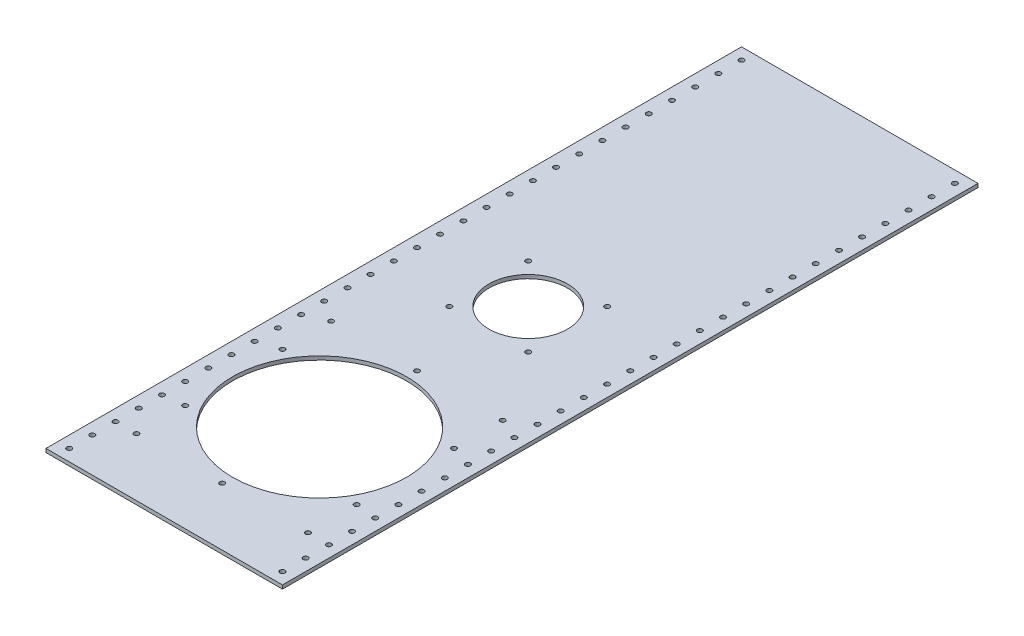
SolidWorks part; units mm, degrees
ref_plane "Front Plane" through (0, 0, 0) normal (0, 0, 1) x (1, 0, 0)
ref_plane "Top Plane" through (0, 0, 0) normal (0, 1, 0) x (1, 0, 0)
ref_plane "Right Plane" through (0, 0, 0) normal (1, 0, 0) x (0, 0, -1)
sketch "Sketch1" plane through (0, 0, 0) normal (0, 1, 0) x (1, 0, 0)
  line L0 (0, 392.549) -> (0, -207.451) construction
  line L1 (-102, -207.451) -> (102, -207.451)
  line L2 (-102, -207.451) -> (-102, 392.549)
  line L3 (-102, 392.549) -> (102, 392.549)
  line L4 (102, -207.451) -> (102, 392.549)
  line L5 (-102, -207.451) -> (102, 392.549) construction
  line L6 (-102, 392.549) -> (102, -207.451) construction
  line L7 (-102, -73.451) -> (102, -73.451) construction
  line L8 (92, 392.549) -> (92, -207.451) construction
  line L9 (-92, 392.549) -> (-92, -207.451) construction
  line L10 (-40, 106.549) -> (40, 106.549) construction
  line L11 (-80, -163.451) -> (80, -163.451) construction
  line L12 (-80, -163.451) -> (-80, 16.549) construction
  line L13 (-80, 16.549) -> (80, 16.549) construction
  line L14 (80, -163.451) -> (80, 16.549) construction
  line L15 (-80, -163.451) -> (80, 16.549) construction
  line L16 (-80, 16.549) -> (80, -163.451) construction
  line L17 (-40, 66.549) -> (40, 66.549) construction
  line L18 (-40, 66.549) -> (-40, 146.549) construction
  line L19 (-40, 146.549) -> (40, 146.549) construction
  line L20 (40, 66.549) -> (40, 146.549) construction
  line L21 (-40, 66.549) -> (40, 146.549) construction
  line L22 (-40, 146.549) -> (40, 66.549) construction
  circle A232 centre (92, 382.549) radius 2.15
  circle A233 centre (92, 362.549) radius 2.15
  circle A234 centre (92, 342.549) radius 2.15
  circle A235 centre (92, 322.549) radius 2.15
  circle A236 centre (92, 302.549) radius 2.15
  circle A237 centre (92, 282.549) radius 2.15
  circle A238 centre (92, 262.549) radius 2.15
  circle A239 centre (92, 242.549) radius 2.15
  circle A240 centre (92, 222.549) radius 2.15
  circle A241 centre (92, 202.549) radius 2.15
  circle A242 centre (92, 182.549) radius 2.15
  circle A243 centre (92, 162.549) radius 2.15
  circle A244 centre (92, 142.549) radius 2.15
  circle A245 centre (92, 122.549) radius 2.15
  circle A246 centre (92, 102.549) radius 2.15
  circle A247 centre (92, 82.549) radius 2.15
  circle A248 centre (92, 62.549) radius 2.15
  circle A249 centre (92, 42.549) radius 2.15
  circle A250 centre (92, 22.549) radius 2.15
  circle A251 centre (92, 2.549) radius 2.15
  circle A252 centre (92, -17.451) radius 2.15
  circle A253 centre (92, -37.451) radius 2.15
  circle A254 centre (92, -57.451) radius 2.15
  circle A255 centre (92, -77.451) radius 2.15
  circle A256 centre (92, -97.451) radius 2.15
  circle A257 centre (92, -117.451) radius 2.15
  circle A258 centre (92, -137.451) radius 2.15
  circle A259 centre (92, -157.451) radius 2.15
  circle A260 centre (92, -177.451) radius 2.15
  circle A261 centre (92, -197.451) radius 2.15
  circle A262 centre (-92, -197.451) radius 2.15
  circle A263 centre (-92, -177.451) radius 2.15
  circle A264 centre (-92, -157.451) radius 2.15
  circle A265 centre (-92, -137.451) radius 2.15
  circle A266 centre (-92, -117.451) radius 2.15
  circle A267 centre (-92, -97.451) radius 2.15
  circle A268 centre (-92, -77.451) radius 2.15
  circle A269 centre (-92, -57.451) radius 2.15
  circle A270 centre (-92, -37.451) radius 2.15
  circle A271 centre (-92, -17.451) radius 2.15
  circle A272 centre (-92, 2.549) radius 2.15
  circle A273 centre (-92, 22.549) radius 2.15
  circle A274 centre (-92, 42.549) radius 2.15
  circle A275 centre (-92, 62.549) radius 2.15
  circle A276 centre (-92, 82.549) radius 2.15
  circle A277 centre (-92, 102.549) radius 2.15
  circle A278 centre (-92, 122.549) radius 2.15
  circle A279 centre (-92, 142.549) radius 2.15
  circle A280 centre (-92, 162.549) radius 2.15
  circle A281 centre (-92, 182.549) radius 2.15
  circle A282 centre (-92, 202.549) radius 2.15
  circle A283 centre (-92, 222.549) radius 2.15
  circle A284 centre (-92, 242.549) radius 2.15
  circle A285 centre (-92, 262.549) radius 2.15
  circle A286 centre (-92, 282.549) radius 2.15
  circle A287 centre (-92, 302.549) radius 2.15
  circle A288 centre (-92, 322.549) radius 2.15
  circle A289 centre (-92, 342.549) radius 2.15
  circle A290 centre (-92, 362.549) radius 2.15
  circle A291 centre (-92, 382.549) radius 2.15
  circle A292 centre (0, -73.451) radius 62.5 construction
  circle A293 centre (-74, -157.451) radius 2.125
  circle A294 centre (-74, -115.451) radius 2.125
  circle A296 centre (0, -157.451) radius 2.125
  circle A297 centre (74, -157.451) radius 2.125
  circle A298 centre (74, -115.451) radius 2.125
  circle A299 centre (74, -31.451) radius 2.125
  circle A300 centre (74, 10.549) radius 2.125
  circle A301 centre (0, 10.549) radius 2.125
  circle A302 centre (-74, 10.549) radius 2.125
  circle A303 centre (-74, -31.451) radius 2.125
  circle A304 centre (0, 106.549) radius 33.85
  circle A310 centre (0, -73.451) radius 75.125
  circle A313 centre (-34, 72.549) radius 2.15
  circle A314 centre (34, 72.549) radius 2.15
  circle A315 centre (34, 140.549) radius 2.15
  circle A316 centre (-34, 140.549) radius 2.15
  point P175 (0, -253.451)
  point P177 (0, 51.2899)
  dimension "D3" = 10
  dimension "D8" = 180
  dimension "D9" = 4.25
  dimension "D11" = 6
  dimension "D16" = 150.25
  dimension "D17" = 4.25
  dimension "D19" = 180
  dimension "D21" = 80
  dimension "D4" = 4.3
  dimension "D6" = 125
  dimension "D13" = 4.25
  dimension "D20" = 80
  dimension "D22" = 67.7
  dimension "D23" = 73.451
  dimension "D25" = 4.3
  dimension "D2" = 600
  dimension "D5" = 10
  dimension "D7" = 160
  dimension "D12" = 42
  dimension "D15" = 134
  dimension "D18" = 6
  dimension "D24" = 204
  dimension "D10" = 6
  dimension "D14" = 0
  dimension "D26" = 6
  dimension "D27" = 6
extrude "Boss-Extrude1" add sketch "Sketch1" along normal blind 3.175
equation "\"m3\"=3.2"
